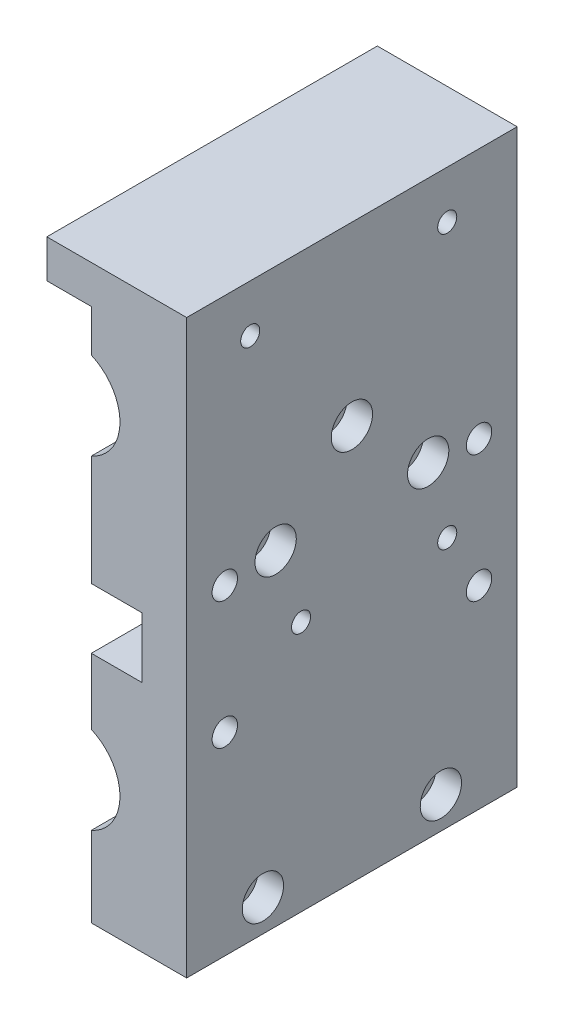
SolidWorks part; units mm, degrees
material "ABS"
ref_plane "Front Plane" through (0, 0, 0) normal (0, 0, 1) x (1, 0, 0)
ref_plane "Top Plane" through (0, 0, 0) normal (0, 1, 0) x (1, 0, 0)
ref_plane "Right Plane" through (0, 0, 0) normal (1, 0, 0) x (0, 0, -1)
sketch "Sketch1" plane through (0, 0, 0) normal (0, 0, 1) x (1, 0, 0)
  line L0 (0, 0) -> (0, -37.75)
  line L1 (0, -37.75) -> (8, -37.75)
  line L2 (8, -37.75) -> (8, -47.25)
  line L3 (8, -47.25) -> (0, -47.25)
  line L4 (0, -47.25) -> (0, -84)
  line L5 (0, -84) -> (15, -84)
  line L6 (15, -84) -> (15, 6)
  line L7 (15, 6) -> (-7, 6)
  line L8 (-7, 6) -> (-7, 0)
  line L9 (-7, 0) -> (0, 0)
  dimension "D1" = 15
  dimension "D2" = 8
  dimension "D3" = 7
  dimension "D4" = 6
  dimension "D5" = 37.75
  dimension "D6" = 90
  dimension "D7" = 9.5
extrude "Boss-Extrude1" add sketch "Sketch1" along normal blind 52
sketch "Sketch2" plane through (0, 0, 0) normal (-1, 0, 0) x (0, 0, 1)
  line L0 (52, 6) -> (0, 6) construction
  line L1 (52, 0) -> (52, -37.75) construction
  line L2 (26, 6) -> (26, -173.9913) construction
  circle A0 centre (26, -21.75) radius 2
  circle A1 centre (38, -32.75) radius 2
  circle A2 centre (14, -32.75) radius 2
  dimension "D1" = 27.75
  dimension "D2" = 4
  dimension "D3" = 26
  dimension "D4" = 24
  dimension "D5" = 12
  dimension "D6" = 38.75
extrude "Cut-Extrude1" cut sketch "Sketch2" against normal through all
sketch "Esquisse1" plane through (15, 0, 0) normal (1, 0, 0) x (0, 0, -1)
  line L0 (-52, -84) -> (-52, 6) construction
  line L1 (-52, 6) -> (0, 6) construction
  circle A0 centre (-42, -1.5) radius 1.5
  circle A1 centre (-11, -1.5) radius 1.5
  circle A4 centre (-34, -44.5) radius 1.5
  circle A5 centre (-11, -44.5) radius 1.5
  dimension "D1" = 10
  dimension "D2" = 7.5
  dimension "D3" = 31
  dimension "D4" = 43
  dimension "D5" = 3
  dimension "D6" = 8
  dimension "D7" = 23
extrude "Enlèv. mat.-Extru.1" cut sketch "Esquisse1" against normal through all
sketch "Esquisse2" plane through (0, 0, 0) normal (-1, 0, 0) x (0, 0, 1)
  circle A0 centre (42, -1.5) radius 2.5
  circle A1 centre (11, -1.5) radius 2.5
  dimension "D1" = 5
extrude "Enlèv. mat.-Extru.2" cut sketch "Esquisse2" against normal blind 3 and the other way through all
sketch "Esquisse3" plane through (15, 0, 0) normal (1, 0, 0) x (0, 0, -1)
  circle A0 centre (-26, -21.75) radius 3.25
  circle A1 centre (-14, -32.75) radius 3.25
  circle A2 centre (-38, -32.75) radius 3.25
  dimension "D1" = 6.5
extrude "Enlèv. mat.-Extru.3" cut sketch "Esquisse3" against normal blind 4
sketch "Esquisse4" plane through (15, 0, 0) normal (1, 0, 0) x (0, 0, -1)
  line L0 (-52, -84) -> (-52, 6) construction
  line L1 (0, -84) -> (0, 6) construction
  line L2 (-52, -84) -> (0, -84) construction
  circle A0 centre (-40, -79) radius 2
  circle A1 centre (-12, -79) radius 2
  circle A2 centre (-12, -79) radius 3.25
  circle A3 centre (-40, -79) radius 3.25
  dimension "D1" = 4
  dimension "D2" = 12
  dimension "D3" = 12
  dimension "D4" = 5
  dimension "D5" = 6.5
extrude "Enlèv. mat.-Extru.4" cut sketch "Esquisse4" against normal through all contours A0 | A1 region at (15, -79, 40) region at (15, -79, 12)
extrude "Enlèv. mat.-Extru.5" cut sketch "Esquisse4<3>" against normal blind 4
sketch "Esquisse4<3>" plane through (15, 0, 0) normal (1, 0, 0) x (0, 0, -1) same geometry as "Esquisse4"
sketch "Esquisse5" plane through (0, 0, 0) normal (-1, 0, 0) x (0, 0, 1)
  line L0 (52, 6) -> (0, 6) construction
  line L1 (52, 0) -> (52, -37.75) construction
  line L2 (0, 0) -> (0, -37.75) construction
  circle A0 centre (46, -33.5) radius 2
  circle A1 centre (6, -33.5) radius 2
  dimension "D1" = 4
  dimension "D2" = 39.5
  dimension "D3" = 6
  dimension "D4" = 6
extrude "Enlèv. mat.-Extru.6" cut sketch "Esquisse5" against normal through all
sketch "Esquisse6" plane through (15, 0, 0) normal (1, 0, 0) x (0, 0, -1)
  line L0 (0, -84) -> (0, 6) construction
  line L1 (-52, -84) -> (-52, 6) construction
  circle A0 centre (-6, -53.5) radius 2
  circle A1 centre (-46, -53.5) radius 2
  circle A2 centre (-6, -33.5) radius 2 construction
  dimension "D1" = 20
  dimension "D2" = 4
  dimension "D3" = 6
  dimension "D4" = 6
extrude "Enlèv. mat.-Extru.7" cut sketch "Esquisse6" against normal through all
sketch "Esquisse7" plane through (0, 0, 0) normal (-1, 0, 0) x (0, 0, 1)
  circle A0 centre (46, -53.5) radius 3.25
  circle A1 centre (6, -53.5) radius 3.25
  dimension "D1" = 6.5
extrude "Enlèv. mat.-Extru.8" cut sketch "Esquisse7" against normal blind 4
sketch "Esquisse8" plane through (0, 0, 0) normal (0, 0, -1) x (-1, 0, 0)
  line L0 (-15, 6) -> (7, 6) construction
  line L1 (-15, -84) -> (-15, 6) construction
  line L2 (0, -84) -> (-15, -84) construction
  circle A0 centre (3, -13.5) radius 7.5
  circle A1 centre (3, -64.5) radius 7.5
  dimension "D1" = 19.5
  dimension "D2" = 18
  dimension "D3" = 15
  dimension "D4" = 19.5
extrude "Enlèv. mat.-Extru.9" cut sketch "Esquisse8" against normal through all
ref_plane "Plan1" through (0, 0, 26) normal (0, 0, 1) x (1, 0, 0)
ref_plane "Plan8" through (0, -39, 0) normal (0, 1, 0) x (1, 0, 0)
